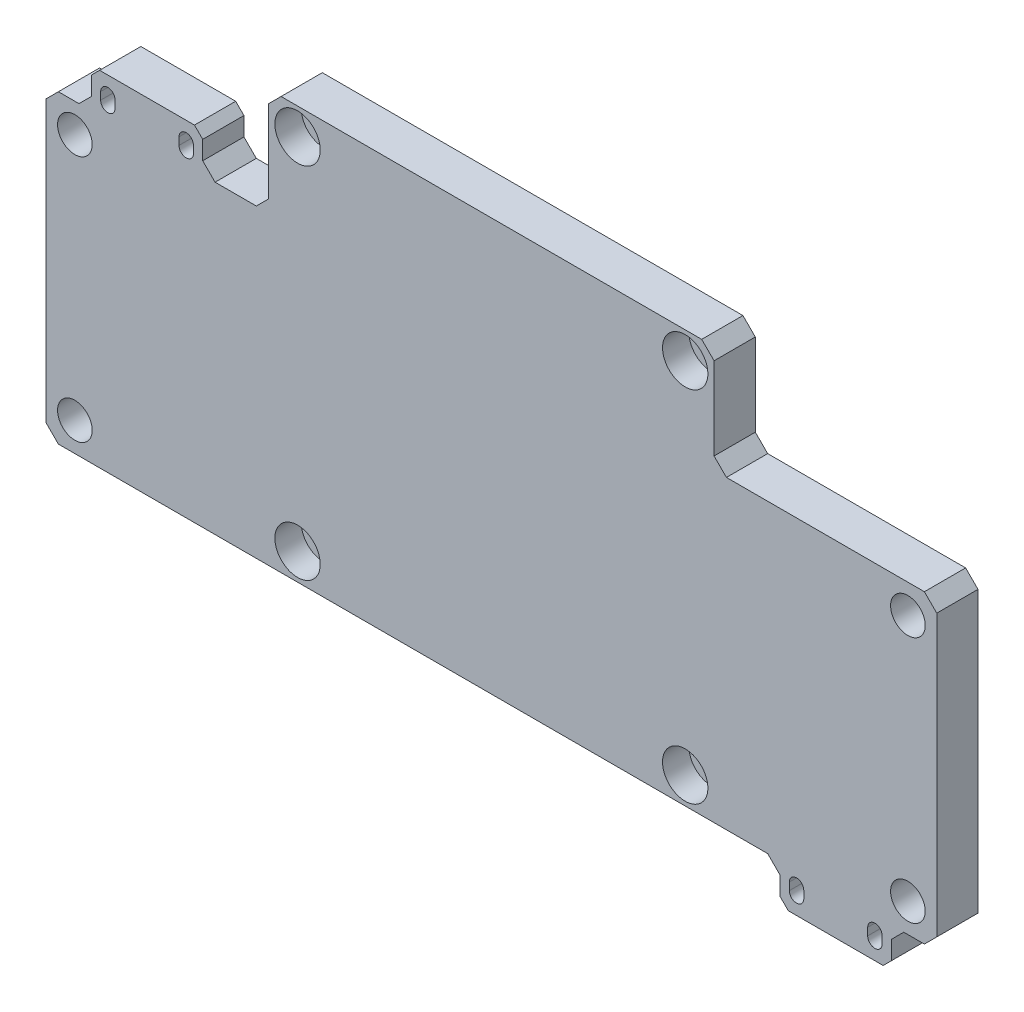
SolidWorks part; units mm, degrees
material "ABS"
ref_plane "Ebene vorne" through (0, 0, 0) normal (0, 0, 1) x (1, 0, 0)
ref_plane "Ebene oben" through (0, 0, 0) normal (0, 1, 0) x (1, 0, 0)
ref_plane "Ebene rechts" through (0, 0, 0) normal (1, 0, 0) x (0, 0, -1)
sketch "Skizze1" plane through (0, 0, 0) normal (0, 0, 1) x (1, 0, 0)
  line L1 (108, -50) -> (-108, -50)
  line L2 (108, -50) -> (108, 50)
  line L3 (108, 50) -> (-108, 50)
  line L4 (-108, -50) -> (-108, 50)
  line L5 (108, -50) -> (-108, 50) construction
  line L6 (108, 50) -> (-108, -50) construction
  point P0 (0, 0)
  dimension "D1" = 100
  dimension "D2" = 216
extrude "Aufsatz-Linear austragen1" add sketch "Skizze1" along normal blind 10
sketch "Skizze2" plane through (0, 0, 10) normal (0, 0, 1) x (1, 0, 0)
  line L1 (47, -43.5) -> (-47, -43.5)
  line L2 (47, -43.5) -> (47, 43.5)
  line L3 (47, 43.5) -> (-47, 43.5)
  line L4 (-47, -43.5) -> (-47, 43.5)
  line L5 (47, -43.5) -> (-47, 43.5) construction
  line L6 (47, 43.5) -> (-47, -43.5) construction
  point P0 (0, 0)
  dimension "D1" = 94
  dimension "D2" = 87
hole_wizard "Stirnsenkung für M6 Zylinderschraube mit Innensechskant1" positions "Skizze3" profile "Skizze4" counterbore size "M6" standard "DIN"
sketch "Skizze3" plane through (0, 0, 10) normal (0, 0, 1) x (1, 0, 0)
  point P0 (-47, -43.5)
  point P3 (47, -43.5)
sketch "Skizze4" plane through (-47, -43.5, 10) normal (1, 0, 0) x (0, -1, 0)
  line L0 (0, 0) -> (0, 16.9828)
  line L1 (0, 16.9828) -> (3.3, 15)
  line L2 (3.3, 15) -> (3.3, 6.4)
  line L3 (3.3, 6.4) -> (5.5, 6.4)
  line L4 (5.5, 6.4) -> (5.5, 0)
  line L5 (5.5, 0) -> (0, 0)
  line L10 (0, 16.9828) -> (-3.3, 15) construction
  line L11 (0, -6.35) -> (0, 107.95) construction
  dimension "Bohrerdurchmesser" = 6.6
  dimension "Bohrungstiefe" = 15
  dimension "Senkdurchmesser2" = 11
  dimension "Senktiefe2" = 6.4
  dimension "Spitzenwinkel" = 118
hole_wizard "CBORE for M6 Hex Socket Head Cap Screw1" positions "Skizze5" profile "Skizze6" counterbore size "M6" standard "DIN"
sketch "Skizze5" plane through (0, 0, 10) normal (0, 0, 1) x (1, 0, 0)
  point P0 (-47, 43.5)
  point P3 (47, 43.5)
sketch "Skizze6" plane through (-47, 43.5, 10) normal (1, 0, 0) x (0, -1, 0)
  line L0 (0, 0) -> (0, 16.9828)
  line L1 (0, 16.9828) -> (3.3, 15)
  line L2 (3.3, 15) -> (3.3, 6.4)
  line L3 (3.3, 6.4) -> (5.5, 6.4)
  line L4 (5.5, 6.4) -> (5.5, 0)
  line L5 (5.5, 0) -> (0, 0)
  line L10 (0, 16.9828) -> (-3.3, 15) construction
  line L11 (0, -6.35) -> (0, 107.95) construction
  dimension "Hole Dia." = 6.6
  dimension "Hole Depth" = 15
  dimension "C'Bore Dia." = 11
  dimension "C'Bore Depth" = 6.4
  dimension "Drill Angle" = 118
sketch "Skizze15" plane through (0, 0, 10) normal (0, 0, 1) x (1, 0, 0)
  line L0 (-108, -50) -> (108, -50) construction
  line L1 (101, -43) -> (-101, -43)
  line L2 (101, -43) -> (101, 17)
  line L3 (101, 17) -> (-101, 17)
  line L4 (-101, -43) -> (-101, 17)
  circle A0 centre (-47, 43.5) radius 3.3 construction
  dimension "D1" = 60
  dimension "D2" = 202
  dimension "D3" = 7
  dimension "D4" = 54
hole_wizard "M8 Clearance Hole1" positions "Skizze16" profile "Skizze17" hole size "M8" standard "ISO"
sketch "Skizze16" plane through (0, 0, 10) normal (0, 0, 1) x (1, 0, 0)
  point P0 (-101, 17)
  point P3 (-101, -43)
  point P6 (101, 17)
  point P9 (101, -43)
sketch "Skizze17" plane through (-101, 17, 10) normal (1, 0, 0) x (0, -1, 0)
  line L0 (0, 0) -> (0, 19.5236)
  line L1 (0, 19.5236) -> (4.2, 17)
  line L2 (4.2, 17) -> (4.2, 0)
  line L5 (4.2, 0) -> (0, 0)
  line L10 (0, 19.5236) -> (-4.2, 17) construction
  line L11 (0, -6.35) -> (0, 107.95) construction
  dimension "Bohrerdurchmesser" = 8.4
  dimension "Bohrungstiefe" = 17
  dimension "Spitzenwinkel" = 118
sketch "Skizze18" plane through (0, 0, 10) normal (0, 0, 1) x (1, 0, 0)
  line L0 (-108, -50) -> (108, -50) construction
  line L1 (-108, 50) -> (-54, 50)
  line L2 (-108, 50) -> (-108, 24)
  line L3 (-108, 24) -> (-54, 24)
  line L4 (-54, 50) -> (-54, 24)
  dimension "D1" = 74
  dimension "D2" = 54
extrude "Schnitt-Linear austragen1" cut sketch "Skizze18" against normal blind 15
mirror "Spiegeln1" about plane through (0, 0, 0) normal (1, 0, 0) of "Schnitt-Linear austragen1"
sketch "Sketch1" plane through (0, 24, 0) normal (0, 1, 0) x (1, 0, 0)
  line L0 (108, 0) -> (54, 0) construction
  line L1 (97, 0) -> (70, 0)
  line L2 (97, 0) -> (97, -10)
  line L3 (97, -10) -> (70, -10)
  line L4 (70, 0) -> (70, -10)
  line L5 (108, -10) -> (54, -10) construction
  line L7 (0, -55) -> (0, 55) construction
  dimension "D1" = 70
  dimension "D2" = 27
extrude "Boss-Extrude1" add sketch "Sketch1" along normal blind 9.5
sketch "Sketch3" plane through (0, 0, 0) normal (0, 0, -1) x (-1, 0, 0)
  line L0 (-93, 29.15) -> (-93, 27.35) construction
  line L1 (-91.25, 29.15) -> (-91.25, 27.35)
  line L2 (-94.75, 29.15) -> (-94.75, 27.35)
  line L4 (-97, 33.5) -> (-70, 33.5) construction
  line L5 (-97, 33.5) -> (-97, 24) construction
  arc A0 (-91.25, 29.15) -> (-94.75, 29.15) centre (-93, 29.15) ccw
  arc A1 (-94.75, 27.35) -> (-91.25, 27.35) centre (-93, 27.35) ccw
  point P2 (-93, 28.25)
  dimension "D1" = 3.5
  dimension "D2" = 1.8
  dimension "D3" = 5.25
  dimension "D4" = 4
extrude "Cut-Extrude1" cut sketch "Sketch3" against normal blind 10
pattern_linear "LPattern1" count 2 spacing 19 along (-1, 0, 0) of "Cut-Extrude1"
sketch "Sketch4" plane through (0, 0, 10) normal (0, 0, 1) x (1, 0, 0)
  line L1 (74, 32.3832) -> (71.2, 30.7666)
  line L2 (71.2, 30.7666) -> (71.2, 28.3753)
  line L5 (76.8, 28.3728) -> (76.8, 30.7666)
  line L6 (76.8, 30.7666) -> (74, 32.3832)
  line L7 (71.2, 27.5334) -> (74, 25.9168) [skipped]
  line L8 (74, 25.9168) -> (76.8, 27.5334) [skipped]
  line L16 (74, 24.1168) -> (76.8, 25.7334)
  line L18 (76.8, 25.7334) -> (76.8, 28.3728)
  line L21 (71.2, 28.3753) -> (71.2, 25.7334)
  line L22 (71.2, 25.7334) -> (74, 24.1168)
  line L23 (74, 30.5832) -> (71.2, 28.9666) [skipped]
  line L24 (76.8, 28.9666) -> (74, 30.5832) [skipped]
  circle A0 centre (74, 29.15) radius 2.8 construction
  circle A1 centre (74, 27.35) radius 2.8 construction
  dimension "D2" = 5.6
  dimension "D1" = 5.6
extrude "Cut-Extrude2" cut sketch "Sketch4" along normal blind 3 from offset 10 offset against normal yes
pattern_linear "LPattern2" count 2 spacing 19 along (1, 0, 0) of "Cut-Extrude2"
ref_plane "Plane1" through (0, -13, 0) normal (0, 1, 0) x (1, 0, 0)
mirror "Mirror1" about plane through (0, -13, 0) normal (0, 1, 0) of "LPattern2", "Cut-Extrude2", "LPattern1", "Cut-Extrude1", "Boss-Extrude1"
sketch "Sketch5" plane through (0, 0, 10) normal (0, 0, 1) x (1, 0, 0)
  line L1 (70, 33.5) -> (97, 33.5)
  line L2 (70, 33.5) -> (70, 24)
  line L3 (70, 24) -> (97, 24)
  line L4 (97, 33.5) -> (97, 24)
extrude "Cut-Extrude3" cut sketch "Sketch5" against normal blind 10
sketch "Sketch6" plane through (0, 0, 10) normal (0, 0, 1) x (1, 0, 0)
  line L1 (54, 24) -> (84, 24)
  line L2 (54, 24) -> (54, 59)
  line L3 (54, 59) -> (84, 59)
  line L4 (84, 24) -> (84, 59)
  circle A0 centre (69, 55) radius 1.75
  circle A1 centre (69, 47) radius 1.75
  dimension "D3" = 3.5
  dimension "D4" = 3.5
  dimension "D7" = 4
  dimension "D8" = 8
  dimension "D1" = 30
  dimension "D2" = 35
  dimension "D5" = 15
  dimension "D6" = 15
mirror "Mirror2" about plane through (0, 0, 0) normal (1, 0, 0) of "LPattern2", "LPattern1", "Cut-Extrude1", "Boss-Extrude1", "Cut-Extrude2"
ref_plane "Plane2" through (0, 0, 20) normal (0, 0, 1) x (1, 0, 0)
chamfer "Chamfer1" distance 3 angle 45 4 edges at (-70, 24, 5) (-97, 24, 5) (97, -50, 5) (70, -50, 5)
chamfer "Chamfer3" distance 2 angle 45 4 edges at (-97, 33.5, 5) (-70, 33.5, 5) (70, -59.5, 5) (97, -59.5, 5)
chamfer "Chamfer4" distance 3 angle 45 2 edges at (-54, 24, 5) (54, 24, 5)
sketch "Sketch8" plane through (0, 0, 10) normal (0, 0, 1) x (1, 0, 0)
  line L0 (-54, 38.5) -> (54, 38.5) construction
  line L1 (-54, 27) -> (-54, 50) construction
  line L2 (54, 27) -> (54, 50) construction
  text T0 "<b>CAROLOGISTICS</b>" font "Century Gothic" height 8
chamfer "Chamfer5" distance 3 angle 45 6 edges at (-54, 50, 5) (54, 50, 5) (108, -50, 5) (108, 24, 5) (-108, -50, 5) (-108, 24, 5)
